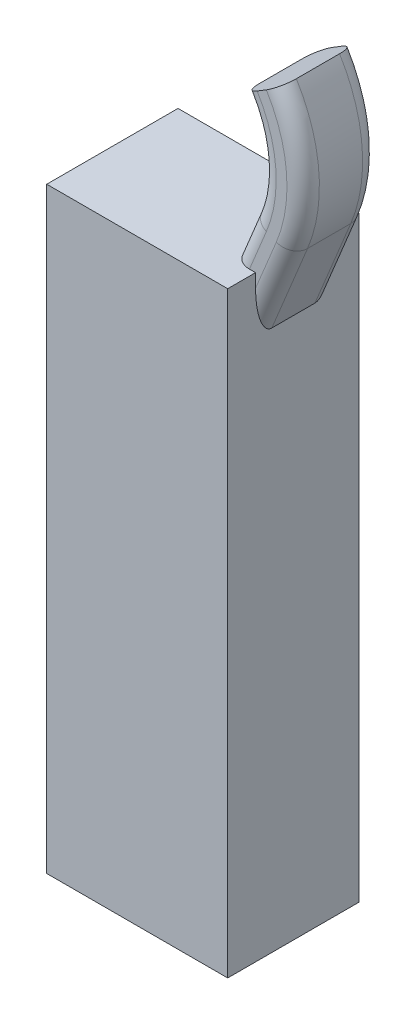
SolidWorks part; units mm, degrees
ref_plane "Front" through (0, 0, 0) normal (0, 0, 1) x (1, 0, 0)
ref_plane "Top" through (0, 0, 0) normal (0, 1, 0) x (1, 0, 0)
ref_plane "Right" through (0, 0, 0) normal (1, 0, 0) x (0, 0, -1)
sketch "Sketch1" plane through (0, 0, 0) normal (0, 0, 1) x (1, 0, 0)
  line L1 (-16.75, -55.25) -> (16.75, -55.25)
  line L2 (-16.75, -55.25) -> (-16.75, 55.25)
  line L3 (-16.75, 55.25) -> (16.75, 55.25)
  line L4 (16.75, -55.25) -> (16.75, 55.25)
  line L5 (-16.75, -55.25) -> (16.75, 55.25) construction
  line L6 (-16.75, 55.25) -> (16.75, -55.25) construction
  point P0 (0, 0)
  dimension "D1" = 33.5
  dimension "D2" = 110.5
extrude "Body" add sketch "Sketch1" along normal mid plane 24.3
sketch "Sketch2" plane through (0, 0, 0) normal (0, 0, 1) x (1, 0, 0)
  line L0 (10.9171, 41.2177) -> (19.6805, 62.4579)
  arc A0 (19.6805, 62.4579) -> (17.8981, 85.0348) centre (-3.4283, 71.9923) ccw
extrude "Cable" add sketch "Sketch2" along normal mid plane 14 thin thin type mid plane wall 8
fillet "Fillet1" radius 3 8 edges at (20.0641, 52.8998, -7) (20.0641, 52.8998, 7) (14.1812, 59.6167, -7) (14.1812, 59.6167, 7) (25.4802, 74.2745, -7) (25.4802, 74.2745, 7) (17.505, 73.6449, -7) (17.505, 73.6449, 7)
